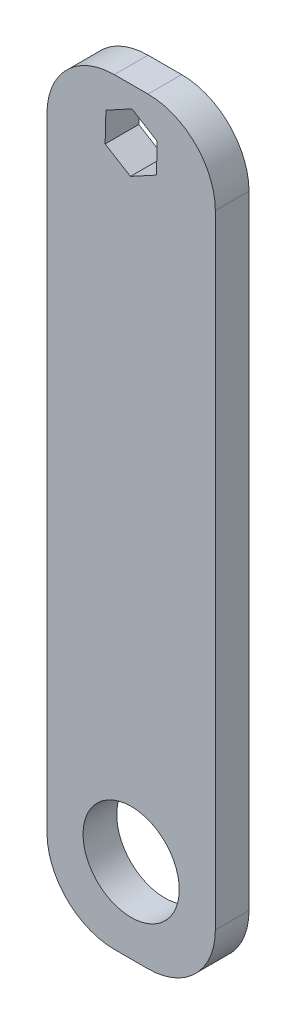
SolidWorks part; units mm, degrees
ref_plane "Front Plane" through (0, 0, 0) normal (0, 0, 1) x (1, 0, 0)
ref_plane "Top Plane" through (0, 0, 0) normal (0, 1, 0) x (1, 0, 0)
ref_plane "Right Plane" through (0, 0, 0) normal (1, 0, 0) x (0, 0, -1)
sketch "Sketch1" plane through (0, 0, 0) normal (0, 1, 0) x (1, 0, 0)
  line L1 (-25, -5) -> (25, -5)
  line L2 (-25, -5) -> (-25, 5)
  line L3 (-25, 5) -> (25, 5)
  line L4 (25, -5) -> (25, 5)
  line L5 (-25, -5) -> (25, 5) construction
  line L6 (-25, 5) -> (25, -5) construction
  point P0 (0, 0)
  dimension "D1" = 50
  dimension "D2" = 10
extrude "Boss-Extrude1" add sketch "Sketch1" along normal mid plane 225
sketch "Sketch2" plane through (0, 0, 5) normal (0, 0, 1) x (1, 0, 0)
  line L0 (0, -55) -> (0, 55) construction
  line L1 (7.5041, 92.904) -> (7.7323, 101.7007)
  line L2 (7.7323, 101.7007) -> (0.2282, 106.2967)
  line L3 (0.2282, 106.2967) -> (-7.5041, 102.096)
  line L4 (-7.5041, 102.096) -> (-7.7323, 93.2993)
  line L5 (-7.7323, 93.2993) -> (-0.2282, 88.7033)
  line L6 (-0.2282, 88.7033) -> (7.5041, 92.904)
  line L7 (-25, 112.5) -> (25, 112.5) construction
  line L8 (-25, -112.5) -> (25, -112.5) construction
  circle A0 centre (0, 97.5) radius 7.6207 construction
  circle A2 centre (0, -87.5) radius 14.2875
  point P14 (0, -87.5)
  point P15 (0, 97.5)
  point P16 (0, 97.5)
  point P24 (0, 97.5)
  dimension "D1" = 15
  dimension "D2" = 25
extrude "Cut-Extrude1" cut sketch "Sketch2" against normal blind 127
fillet "Fillet1" radius 20 4 edges at (-25, -112.5, 0) (25, -112.5, 0) (25, 112.5, 0) (-25, 112.5, 0)
sketch "Sketch4" plane through (0, 0, 0) normal (1, 0, 0) x (0, 0, -1)
  line L0 (-19.057, 97.5) -> (19.6205, 97.5) construction
  line L1 (-5, 112.5) -> (5, 112.5) construction
  dimension "D1" = 15
sketch "Sketch5" plane through (0, 0, -5) normal (0, 0, -1) x (-1, 0, 0)
  line L0 (-5, 112.5) -> (5, 112.5) construction
  point P0 (-0.2282, 106.2967)
  point P4 (-7.1246, 96.8797)
  point P5 (1.6392, 88.4276)
  dimension "D1" = 6.2033
sketch "Sketch6" plane through (-37.2602, 68.5849, 0) normal (-0.4774, 0.8787, 0) x (0.8787, 0.4774, 0)
  point P0 (42.144, 5)
sketch "Sketch7" plane through (0, 0, -5) normal (0, 0, -1) x (-1, 0, 0)
  point P0 (0, 106.3665)
  point P1 (-0.2282, 106.2967)
  point P4 (0.2282, 88.7033)
  dimension "D1" = 17.5993
